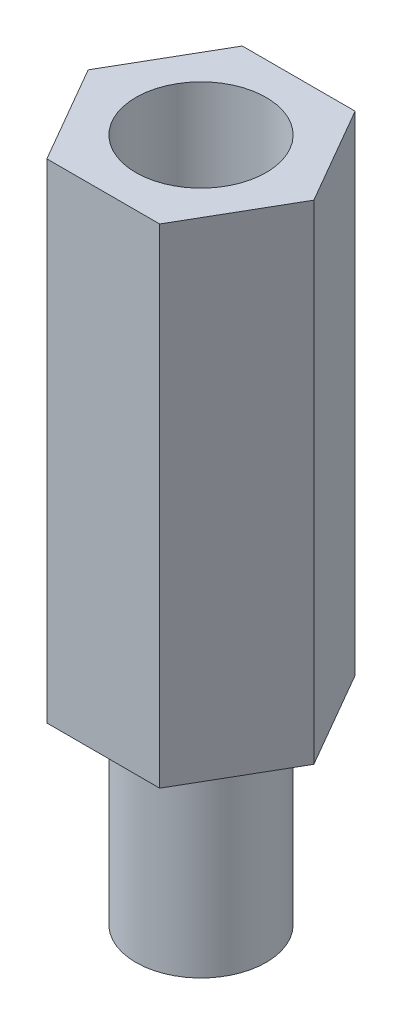
SolidWorks part; units mm, degrees
material "铜"
ref_plane "前视基准面" through (0, 0, 0) normal (0, 0, 1) x (1, 0, 0)
ref_plane "上视基准面" through (0, 0, 0) normal (0, 1, 0) x (1, 0, 0)
ref_plane "右视基准面" through (0, 0, 0) normal (1, 0, 0) x (0, 0, -1)
sketch "草图2" plane through (0, 0, 0) normal (0, 1, 0) x (1, 0, 0)
  line L1 (3.4641, 0) -> (1.7321, 3)
  line L2 (1.7321, 3) -> (-1.7321, 3)
  line L3 (-1.7321, 3) -> (-3.4641, 0)
  line L4 (-3.4641, 0) -> (-1.7321, -3)
  line L5 (-1.7321, -3) -> (1.7321, -3)
  line L6 (1.7321, -3) -> (3.4641, 0)
  circle A0 centre (0, 0) radius 3 construction
  circle A1 centre (0, 0) radius 2
  dimension "D2" = 4
  dimension "D1" = 6
extrude "凸台-拉伸1" add sketch "草图2" along normal blind 15
extrude "凸台-拉伸2" add sketch "草图2<2>" against normal blind 6 separate body contours A1 region at (0, 0, 0)
sketch "草图2<2>" plane through (0, 0, 0) normal (0, 1, 0) x (1, 0, 0) same geometry as "草图2"
